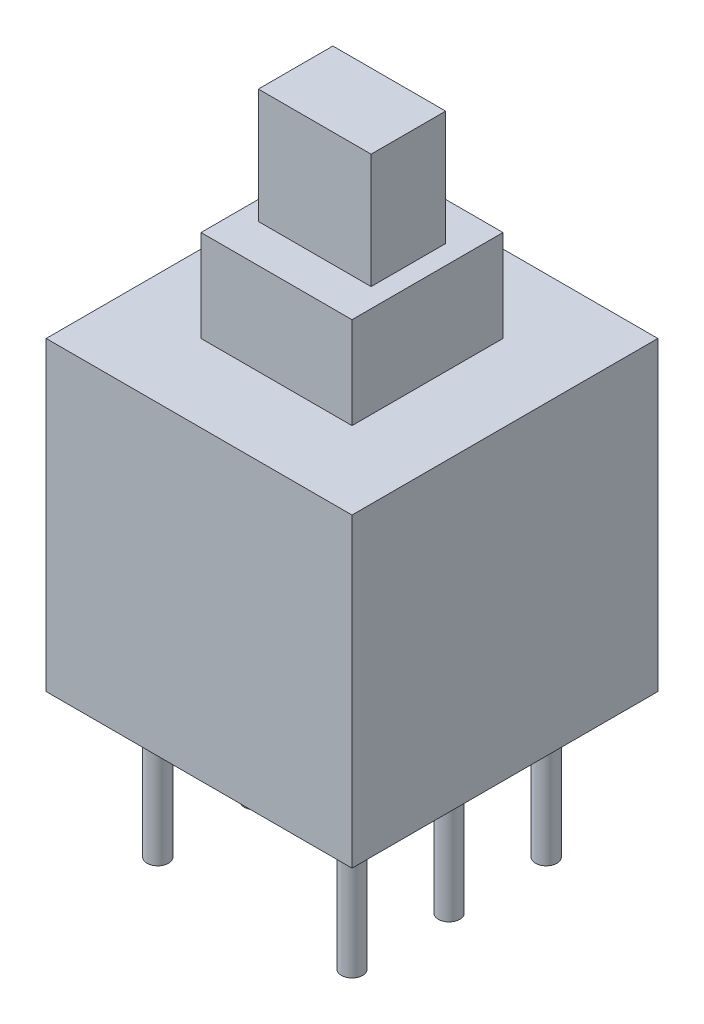
SolidWorks part; units mm, degrees
ref_plane "Front Plane" through (0, 0, 0) normal (0, 0, 1) x (1, 0, 0)
ref_plane "Top Plane" through (0, 0, 0) normal (0, 1, 0) x (1, 0, 0)
ref_plane "Right Plane" through (0, 0, 0) normal (1, 0, 0) x (0, 0, -1)
sketch "Sketch1" plane through (0, 0, 0) normal (0, 1, 0) x (1, 0, 0)
  line L1 (-4, -4) -> (4, -4)
  line L2 (-4, -4) -> (-4, 4)
  line L3 (-4, 4) -> (4, 4)
  line L4 (4, -4) -> (4, 4)
  line L5 (-4, -4) -> (4, 4) construction
  line L6 (-4, 4) -> (4, -4) construction
  point P0 (0, 0)
  dimension "D1" = 8
extrude "Boss-Extrude1" add sketch "Sketch1" along normal blind 8 contours L3 L4 L1 L2
sketch "Sketch2" plane through (0, 8, 0) normal (0, 1, 0) x (1, 0, 0)
  line L1 (-1.975, -1.975) -> (1.975, -1.975)
  line L2 (-1.975, -1.975) -> (-1.975, 1.975)
  line L3 (-1.975, 1.975) -> (1.975, 1.975)
  line L4 (1.975, -1.975) -> (1.975, 1.975)
  line L5 (-1.975, -1.975) -> (1.975, 1.975) construction
  line L6 (-1.975, 1.975) -> (1.975, -1.975) construction
  point P0 (0, 0)
  dimension "D1" = 3.95
extrude "Boss-Extrude2" add sketch "Sketch2" along normal blind 2.4 contours L3 L4 L1 L2
sketch "Sketch3" plane through (0, 10.4, 0) normal (0, 1, 0) x (1, 0, 0)
  line L1 (-1.475, -0.975) -> (1.475, -0.975)
  line L2 (-1.475, -0.975) -> (-1.475, 0.975)
  line L3 (-1.475, 0.975) -> (1.475, 0.975)
  line L4 (1.475, -0.975) -> (1.475, 0.975)
  line L5 (-1.475, -0.975) -> (1.475, 0.975) construction
  line L6 (-1.475, 0.975) -> (1.475, -0.975) construction
  point P0 (0, 0)
  dimension "D1" = 2.95
  dimension "D2" = 1.95
extrude "Boss-Extrude3" add sketch "Sketch3" along normal blind 3 contours L3 L4 L1 L2
sketch "Sketch4" plane through (0, 0, 0) normal (0, -1, 0) x (1, 0, 0)
  line L0 (2.54, 2.54) -> (2.54, 0) construction
  line L1 (2.54, 0) -> (2.54, -2.54) construction
  line L2 (-2.54, 0) -> (2.54, 0) construction
  line L3 (-2.54, -2.54) -> (-2.54, 0) construction
  line L4 (-2.54, 0) -> (-2.54, 2.54) construction
  circle A0 centre (2.54, 2.54) radius 0.28
  circle A1 centre (2.54, 0) radius 0.28
  circle A2 centre (2.54, -2.54) radius 0.28
  circle A3 centre (-2.54, -2.54) radius 0.28
  circle A4 centre (-2.54, 0) radius 0.28
  circle A5 centre (-2.54, 2.54) radius 0.28
  dimension "D3" = 0.56
  dimension "D1" = 2.54
  dimension "D2" = 5.08
extrude "Boss-Extrude4" add sketch "Sketch4" along normal blind 3.75
